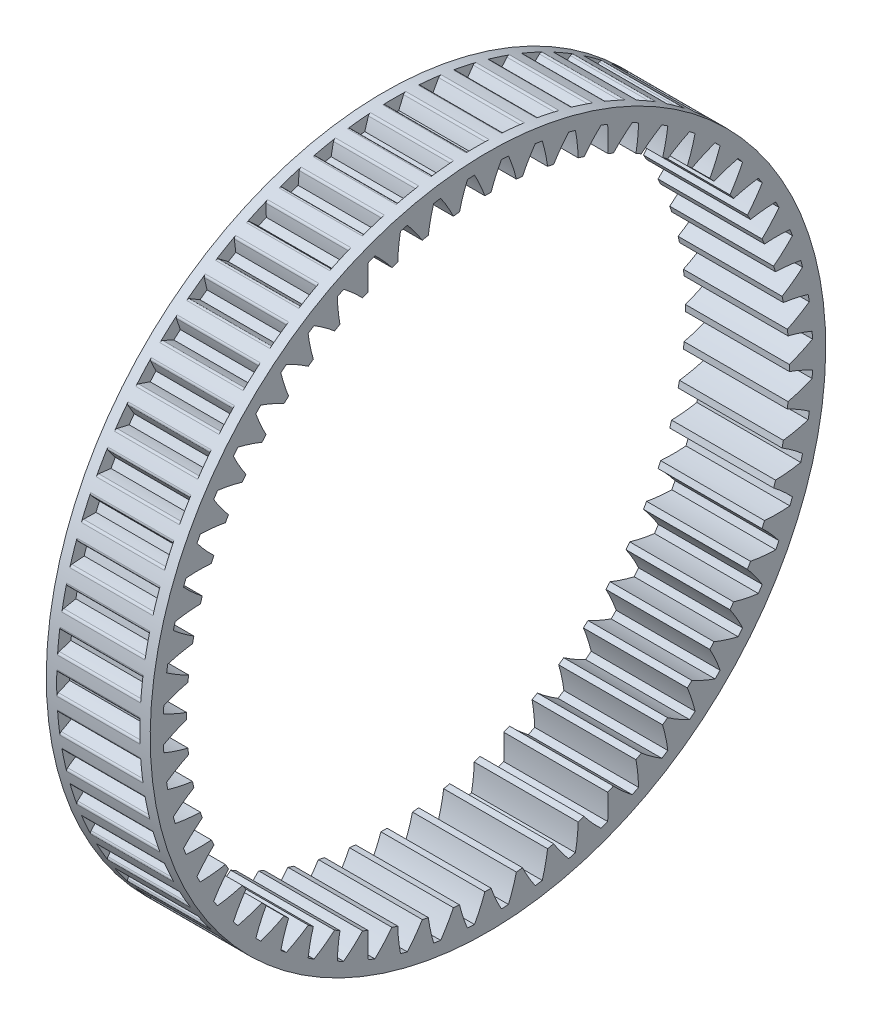
SolidWorks part; units mm, degrees
material "AISI 1020"
ref_plane "Front Plane" through (0, 0, 0) normal (0, 0, 1) x (1, 0, 0)
ref_plane "Top Plane" through (0, 0, 0) normal (0, 1, 0) x (1, 0, 0)
ref_plane "Right Plane" through (0, 0, 0) normal (1, 0, 0) x (0, 0, -1)
ref_plane "Plane1" through (10, 0, 0) normal (1, 0, 0) x (0, 0, -1)
sketch "Sketch1" plane through (10, 0, 0) normal (1, 0, 0) x (0, 0, -1)
  circle A0 centre (0, 0) radius 32.5
  arc A1 (1.8156, 28.9431) -> (2.9287, 31.1135) centre (15.6748, 23.2053) cw
  arc A2 (2.9287, 31.1135) -> (3.6041, 31.0425) centre (0, 0) cw
  arc A3 (3.6041, 31.0425) -> (4.2417, 28.6881) centre (-10.5076, 25.9572) cw
  arc A4 (4.2417, 28.6881) -> (4.831, 28.5948) centre (0, 0) cw
  arc A5 (4.831, 28.5948) -> (6.1649, 30.6369) centre (18.0145, 21.4397) cw
  arc A6 (6.1649, 30.6369) -> (6.8292, 30.4957) centre (0, 0) cw
  arc A7 (6.8292, 30.4957) -> (7.2172, 28.0876) centre (-7.7368, 26.9133) cw
  arc A8 (7.2172, 28.0876) -> (7.7935, 27.9332) centre (0, 0) cw
  arc A9 (7.7935, 27.9332) -> (9.3336, 29.8246) centre (20.1569, 19.4393) cw
  arc A10 (9.3336, 29.8246) -> (9.9794, 29.6148) centre (0, 0) cw
  arc A11 (9.9794, 29.6148) -> (10.1136, 27.1793) centre (-4.8812, 27.5746) cw
  arc A12 (10.1136, 27.1793) -> (10.6706, 26.9655) centre (0, 0) cw
  arc A13 (10.6706, 26.9655) -> (12.4, 28.6856) centre (22.0784, 17.2258) cw
  arc A14 (12.4, 28.6856) -> (13.0204, 28.4094) centre (0, 0) cw
  arc A15 (13.0204, 28.4094) -> (12.8992, 25.9733) centre (-1.9721, 27.9338) cw
  arc A16 (12.8992, 25.9733) -> (13.4308, 25.7024) centre (0, 0) cw
  arc A17 (13.4308, 25.7024) -> (15.3305, 27.2323) centre (23.7581, 14.8236) cw
  arc A18 (15.3305, 27.2323) -> (15.9186, 26.8928) centre (0, 0) cw
  arc A19 (15.9186, 26.8928) -> (15.5435, 24.4826) centre (0.9586, 27.9869) cw
  arc A20 (15.5435, 24.4826) -> (16.0439, 24.1577) centre (0, 0) cw
  arc A21 (16.0439, 24.1577) -> (18.0931, 25.4807) centre (25.1774, 12.259) cw
  arc A22 (18.0931, 25.4807) -> (18.6425, 25.0815) centre (0, 0) cw
  arc A23 (18.6425, 25.0815) -> (18.0175, 22.7238) centre (3.8788, 27.7334) cw
  arc A24 (18.0175, 22.7238) -> (18.4812, 22.3483) centre (0, 0) cw
  arc A25 (18.4812, 22.3483) -> (20.6574, 23.4498) centre (26.3209, 9.5601) cw
  arc A26 (20.6574, 23.4498) -> (21.1621, 22.9954) centre (0, 0) cw
  arc A27 (21.1621, 22.9954) -> (20.2941, 20.7159) centre (6.7564, 27.176) cw
  arc A28 (20.2941, 20.7159) -> (20.7159, 20.2941) centre (0, 0) cw
  arc A29 (20.7159, 20.2941) -> (22.9954, 21.1621) centre (27.176, 6.7564) cw
  arc A30 (22.9954, 21.1621) -> (23.4498, 20.6574) centre (0, 0) cw
  arc A31 (23.4498, 20.6574) -> (22.3483, 18.4812) centre (9.5601, 26.3209) cw
  arc A32 (22.3483, 18.4812) -> (22.7238, 18.0175) centre (0, 0) cw
  arc A33 (22.7238, 18.0175) -> (25.0815, 18.6425) centre (27.7334, 3.8788) cw
  arc A34 (25.0815, 18.6425) -> (25.4807, 18.0931) centre (0, 0) cw
  arc A35 (25.4807, 18.0931) -> (24.1577, 16.0439) centre (12.259, 25.1774) cw
  arc A36 (24.1577, 16.0439) -> (24.4826, 15.5435) centre (0, 0) cw
  arc A37 (24.4826, 15.5435) -> (26.8928, 15.9186) centre (27.9869, 0.9586) cw
  arc A38 (26.8928, 15.9186) -> (27.2323, 15.3305) centre (0, 0) cw
  arc A39 (27.2323, 15.3305) -> (25.7024, 13.4308) centre (14.8236, 23.7581) cw
  arc A40 (25.7024, 13.4308) -> (25.9733, 12.8992) centre (0, 0) cw
  arc A41 (25.9733, 12.8992) -> (28.4094, 13.0204) centre (27.9338, -1.9721) cw
  arc A42 (28.4094, 13.0204) -> (28.6856, 12.4) centre (0, 0) cw
  arc A43 (28.6856, 12.4) -> (26.9655, 10.6706) centre (17.2258, 22.0784) cw
  arc A44 (26.9655, 10.6706) -> (27.1793, 10.1136) centre (0, 0) cw
  arc A45 (27.1793, 10.1136) -> (29.6148, 9.9794) centre (27.5746, -4.8812) cw
  arc A46 (29.6148, 9.9794) -> (29.8246, 9.3336) centre (0, 0) cw
  arc A47 (29.8246, 9.3336) -> (27.9332, 7.7935) centre (19.4393, 20.1569) cw
  arc A48 (27.9332, 7.7935) -> (28.0876, 7.2172) centre (0, 0) cw
  arc A49 (28.0876, 7.2172) -> (30.4957, 6.8292) centre (26.9133, -7.7368) cw
  arc A50 (30.4957, 6.8292) -> (30.6369, 6.1649) centre (0, 0) cw
  arc A51 (30.6369, 6.1649) -> (28.5948, 4.831) centre (21.4397, 18.0145) cw
  arc A52 (28.5948, 4.831) -> (28.6881, 4.2417) centre (0, 0) cw
  arc A53 (28.6881, 4.2417) -> (31.0425, 3.6041) centre (25.9572, -10.5076) cw
  arc A54 (31.0425, 3.6041) -> (31.1135, 2.9287) centre (0, 0) cw
  arc A55 (31.1135, 2.9287) -> (28.9431, 1.8156) centre (23.2053, 15.6748) cw
  arc A56 (28.9431, 1.8156) -> (28.9743, 1.2198) centre (0, 0) cw
  arc A57 (28.9743, 1.2198) -> (31.2492, 0.3395) centre (24.7167, -13.1633) cw
  arc A58 (31.2492, 0.3395) -> (31.2492, -0.3395) centre (0, 0) cw
  arc A59 (31.2492, -0.3395) -> (28.9743, -1.2198) centre (24.7167, 13.1633) cw
  arc A60 (28.9743, -1.2198) -> (28.9431, -1.8156) centre (0, 0) cw
  arc A61 (28.9431, -1.8156) -> (31.1135, -2.9287) centre (23.2053, -15.6748) cw
  arc A62 (31.1135, -2.9287) -> (31.0425, -3.6041) centre (0, 0) cw
  arc A63 (31.0425, -3.6041) -> (28.6881, -4.2417) centre (25.9572, 10.5076) cw
  arc A64 (28.6881, -4.2417) -> (28.5948, -4.831) centre (0, 0) cw
  arc A65 (28.5948, -4.831) -> (30.6369, -6.1649) centre (21.4397, -18.0145) cw
  arc A66 (30.6369, -6.1649) -> (30.4957, -6.8292) centre (0, 0) cw
  arc A67 (30.4957, -6.8292) -> (28.0876, -7.2172) centre (26.9133, 7.7368) cw
  arc A68 (28.0876, -7.2172) -> (27.9332, -7.7935) centre (0, 0) cw
  arc A69 (27.9332, -7.7935) -> (29.8246, -9.3336) centre (19.4393, -20.1569) cw
  arc A70 (29.8246, -9.3336) -> (29.6148, -9.9794) centre (0, 0) cw
  arc A71 (29.6148, -9.9794) -> (27.1793, -10.1136) centre (27.5746, 4.8812) cw
  arc A72 (27.1793, -10.1136) -> (26.9655, -10.6706) centre (0, 0) cw
  arc A73 (26.9655, -10.6706) -> (28.6856, -12.4) centre (17.2258, -22.0784) cw
  arc A74 (28.6856, -12.4) -> (28.4094, -13.0204) centre (0, 0) cw
  arc A75 (28.4094, -13.0204) -> (25.9733, -12.8992) centre (27.9338, 1.9721) cw
  arc A76 (25.9733, -12.8992) -> (25.7024, -13.4308) centre (0, 0) cw
  arc A77 (25.7024, -13.4308) -> (27.2323, -15.3305) centre (14.8236, -23.7581) cw
  arc A78 (27.2323, -15.3305) -> (26.8928, -15.9186) centre (0, 0) cw
  arc A79 (26.8928, -15.9186) -> (24.4826, -15.5435) centre (27.9869, -0.9586) cw
  arc A80 (24.4826, -15.5435) -> (24.1577, -16.0439) centre (0, 0) cw
  arc A81 (24.1577, -16.0439) -> (25.4807, -18.0931) centre (12.259, -25.1774) cw
  arc A82 (25.4807, -18.0931) -> (25.0815, -18.6425) centre (0, 0) cw
  arc A83 (25.0815, -18.6425) -> (22.7238, -18.0175) centre (27.7334, -3.8788) cw
  arc A84 (22.7238, -18.0175) -> (22.3483, -18.4812) centre (0, 0) cw
  arc A85 (22.3483, -18.4812) -> (23.4498, -20.6574) centre (9.5601, -26.3209) cw
  arc A86 (23.4498, -20.6574) -> (22.9954, -21.1621) centre (0, 0) cw
  arc A87 (22.9954, -21.1621) -> (20.7159, -20.2941) centre (27.176, -6.7564) cw
  arc A88 (20.7159, -20.2941) -> (20.2941, -20.7159) centre (0, 0) cw
  arc A89 (20.2941, -20.7159) -> (21.1621, -22.9954) centre (6.7564, -27.176) cw
  arc A90 (21.1621, -22.9954) -> (20.6574, -23.4498) centre (0, 0) cw
  arc A91 (20.6574, -23.4498) -> (18.4812, -22.3483) centre (26.3209, -9.5601) cw
  arc A92 (18.4812, -22.3483) -> (18.0175, -22.7238) centre (0, 0) cw
  arc A93 (18.0175, -22.7238) -> (18.6425, -25.0815) centre (3.8788, -27.7334) cw
  arc A94 (18.6425, -25.0815) -> (18.0931, -25.4807) centre (0, 0) cw
  arc A95 (18.0931, -25.4807) -> (16.0439, -24.1577) centre (25.1774, -12.259) cw
  arc A96 (16.0439, -24.1577) -> (15.5435, -24.4826) centre (0, 0) cw
  arc A97 (15.5435, -24.4826) -> (15.9186, -26.8928) centre (0.9586, -27.9869) cw
  arc A98 (15.9186, -26.8928) -> (15.3305, -27.2323) centre (0, 0) cw
  arc A99 (15.3305, -27.2323) -> (13.4308, -25.7024) centre (23.7581, -14.8236) cw
  arc A100 (13.4308, -25.7024) -> (12.8992, -25.9733) centre (0, 0) cw
  arc A101 (12.8992, -25.9733) -> (13.0204, -28.4094) centre (-1.9721, -27.9338) cw
  arc A102 (13.0204, -28.4094) -> (12.4, -28.6856) centre (0, 0) cw
  arc A103 (12.4, -28.6856) -> (10.6706, -26.9655) centre (22.0784, -17.2258) cw
  arc A104 (10.6706, -26.9655) -> (10.1136, -27.1793) centre (0, 0) cw
  arc A105 (10.1136, -27.1793) -> (9.9794, -29.6148) centre (-4.8812, -27.5746) cw
  arc A106 (9.9794, -29.6148) -> (9.3336, -29.8246) centre (0, 0) cw
  arc A107 (9.3336, -29.8246) -> (7.7935, -27.9332) centre (20.1569, -19.4393) cw
  arc A108 (7.7935, -27.9332) -> (7.2172, -28.0876) centre (0, 0) cw
  arc A109 (7.2172, -28.0876) -> (6.8292, -30.4957) centre (-7.7368, -26.9133) cw
  arc A110 (6.8292, -30.4957) -> (6.1649, -30.6369) centre (0, 0) cw
  arc A111 (6.1649, -30.6369) -> (4.831, -28.5948) centre (18.0145, -21.4397) cw
  arc A112 (4.831, -28.5948) -> (4.2417, -28.6881) centre (0, 0) cw
  arc A113 (4.2417, -28.6881) -> (3.6041, -31.0425) centre (-10.5076, -25.9572) cw
  arc A114 (3.6041, -31.0425) -> (2.9287, -31.1135) centre (0, 0) cw
  arc A115 (2.9287, -31.1135) -> (1.8156, -28.9431) centre (15.6748, -23.2053) cw
  arc A116 (1.8156, -28.9431) -> (1.2198, -28.9743) centre (0, 0) cw
  arc A117 (1.2198, -28.9743) -> (0.3395, -31.2492) centre (-13.1633, -24.7167) cw
  arc A118 (0.3395, -31.2492) -> (-0.3395, -31.2492) centre (0, 0) cw
  arc A119 (-0.3395, -31.2492) -> (-1.2198, -28.9743) centre (13.1633, -24.7167) cw
  arc A120 (-1.2198, -28.9743) -> (-1.8156, -28.9431) centre (0, 0) cw
  arc A121 (-1.8156, -28.9431) -> (-2.9287, -31.1135) centre (-15.6748, -23.2053) cw
  arc A122 (-2.9287, -31.1135) -> (-3.6041, -31.0425) centre (0, 0) cw
  arc A123 (-3.6041, -31.0425) -> (-4.2417, -28.6881) centre (10.5076, -25.9572) cw
  arc A124 (-4.2417, -28.6881) -> (-4.831, -28.5948) centre (0, 0) cw
  arc A125 (-4.831, -28.5948) -> (-6.1649, -30.6369) centre (-18.0145, -21.4397) cw
  arc A126 (-6.1649, -30.6369) -> (-6.8292, -30.4957) centre (0, 0) cw
  arc A127 (-6.8292, -30.4957) -> (-7.2172, -28.0876) centre (7.7368, -26.9133) cw
  arc A128 (-7.2172, -28.0876) -> (-7.7935, -27.9332) centre (0, 0) cw
  arc A129 (-7.7935, -27.9332) -> (-9.3336, -29.8246) centre (-20.1569, -19.4393) cw
  arc A130 (-9.3336, -29.8246) -> (-9.9794, -29.6148) centre (0, 0) cw
  arc A131 (-9.9794, -29.6148) -> (-10.1136, -27.1793) centre (4.8812, -27.5746) cw
  arc A132 (-10.1136, -27.1793) -> (-10.6706, -26.9655) centre (0, 0) cw
  arc A133 (-10.6706, -26.9655) -> (-12.4, -28.6856) centre (-22.0784, -17.2258) cw
  arc A134 (-12.4, -28.6856) -> (-13.0204, -28.4094) centre (0, 0) cw
  arc A135 (-13.0204, -28.4094) -> (-12.8992, -25.9733) centre (1.9721, -27.9338) cw
  arc A136 (-12.8992, -25.9733) -> (-13.4308, -25.7024) centre (0, 0) cw
  arc A137 (-13.4308, -25.7024) -> (-15.3305, -27.2323) centre (-23.7581, -14.8236) cw
  arc A138 (-15.3305, -27.2323) -> (-15.9186, -26.8928) centre (0, 0) cw
  arc A139 (-15.9186, -26.8928) -> (-15.5435, -24.4826) centre (-0.9586, -27.9869) cw
  arc A140 (-15.5435, -24.4826) -> (-16.0439, -24.1577) centre (0, 0) cw
  arc A141 (-16.0439, -24.1577) -> (-18.0931, -25.4807) centre (-25.1774, -12.259) cw
  arc A142 (-18.0931, -25.4807) -> (-18.6425, -25.0815) centre (0, 0) cw
  arc A143 (-18.6425, -25.0815) -> (-18.0175, -22.7238) centre (-3.8788, -27.7334) cw
  arc A144 (-18.0175, -22.7238) -> (-18.4812, -22.3483) centre (0, 0) cw
  arc A145 (-18.4812, -22.3483) -> (-20.6574, -23.4498) centre (-26.3209, -9.5601) cw
  arc A146 (-20.6574, -23.4498) -> (-21.1621, -22.9954) centre (0, 0) cw
  arc A147 (-21.1621, -22.9954) -> (-20.2941, -20.7159) centre (-6.7564, -27.176) cw
  arc A148 (-20.2941, -20.7159) -> (-20.7159, -20.2941) centre (0, 0) cw
  arc A149 (-20.7159, -20.2941) -> (-22.9954, -21.1621) centre (-27.176, -6.7564) cw
  arc A150 (-22.9954, -21.1621) -> (-23.4498, -20.6574) centre (0, 0) cw
  arc A151 (-23.4498, -20.6574) -> (-22.3483, -18.4812) centre (-9.5601, -26.3209) cw
  arc A152 (-22.3483, -18.4812) -> (-22.7238, -18.0175) centre (0, 0) cw
  arc A153 (-22.7238, -18.0175) -> (-25.0815, -18.6425) centre (-27.7334, -3.8788) cw
  arc A154 (-25.0815, -18.6425) -> (-25.4807, -18.0931) centre (0, 0) cw
  arc A155 (-25.4807, -18.0931) -> (-24.1577, -16.0439) centre (-12.259, -25.1774) cw
  arc A156 (-24.1577, -16.0439) -> (-24.4826, -15.5435) centre (0, 0) cw
  arc A157 (-24.4826, -15.5435) -> (-26.8928, -15.9186) centre (-27.9869, -0.9586) cw
  arc A158 (-26.8928, -15.9186) -> (-27.2323, -15.3305) centre (0, 0) cw
  arc A159 (-27.2323, -15.3305) -> (-25.7024, -13.4308) centre (-14.8236, -23.7581) cw
  arc A160 (-25.7024, -13.4308) -> (-25.9733, -12.8992) centre (0, 0) cw
  arc A161 (-25.9733, -12.8992) -> (-28.4094, -13.0204) centre (-27.9338, 1.9721) cw
  arc A162 (-28.4094, -13.0204) -> (-28.6856, -12.4) centre (0, 0) cw
  arc A163 (-28.6856, -12.4) -> (-26.9655, -10.6706) centre (-17.2258, -22.0784) cw
  arc A164 (-26.9655, -10.6706) -> (-27.1793, -10.1136) centre (0, 0) cw
  arc A165 (-27.1793, -10.1136) -> (-29.6148, -9.9794) centre (-27.5746, 4.8812) cw
  arc A166 (-29.6148, -9.9794) -> (-29.8246, -9.3336) centre (0, 0) cw
  arc A167 (-29.8246, -9.3336) -> (-27.9332, -7.7935) centre (-19.4393, -20.1569) cw
  arc A168 (-27.9332, -7.7935) -> (-28.0876, -7.2172) centre (0, 0) cw
  arc A169 (-28.0876, -7.2172) -> (-30.4957, -6.8292) centre (-26.9133, 7.7368) cw
  arc A170 (-30.4957, -6.8292) -> (-30.6369, -6.1649) centre (0, 0) cw
  arc A171 (-30.6369, -6.1649) -> (-28.5948, -4.831) centre (-21.4397, -18.0145) cw
  arc A172 (-28.5948, -4.831) -> (-28.6881, -4.2417) centre (0, 0) cw
  arc A173 (-28.6881, -4.2417) -> (-31.0425, -3.6041) centre (-25.9572, 10.5076) cw
  arc A174 (-31.0425, -3.6041) -> (-31.1135, -2.9287) centre (0, 0) cw
  arc A175 (-31.1135, -2.9287) -> (-28.9431, -1.8156) centre (-23.2053, -15.6748) cw
  arc A176 (-28.9431, -1.8156) -> (-28.9743, -1.2198) centre (0, 0) cw
  arc A177 (-28.9743, -1.2198) -> (-31.2492, -0.3395) centre (-24.7167, 13.1633) cw
  arc A178 (-31.2492, -0.3395) -> (-31.2492, 0.3395) centre (0, 0) cw
  arc A179 (-31.2492, 0.3395) -> (-28.9743, 1.2198) centre (-24.7167, -13.1633) cw
  arc A180 (-28.9743, 1.2198) -> (-28.9431, 1.8156) centre (0, 0) cw
  arc A181 (-28.9431, 1.8156) -> (-31.1135, 2.9287) centre (-23.2053, 15.6748) cw
  arc A182 (-31.1135, 2.9287) -> (-31.0425, 3.6041) centre (0, 0) cw
  arc A183 (-31.0425, 3.6041) -> (-28.6881, 4.2417) centre (-25.9572, -10.5076) cw
  arc A184 (-28.6881, 4.2417) -> (-28.5948, 4.831) centre (0, 0) cw
  arc A185 (-28.5948, 4.831) -> (-30.6369, 6.1649) centre (-21.4397, 18.0145) cw
  arc A186 (-30.6369, 6.1649) -> (-30.4957, 6.8292) centre (0, 0) cw
  arc A187 (-30.4957, 6.8292) -> (-28.0876, 7.2172) centre (-26.9133, -7.7368) cw
  arc A188 (-28.0876, 7.2172) -> (-27.9332, 7.7935) centre (0, 0) cw
  arc A189 (-27.9332, 7.7935) -> (-29.8246, 9.3336) centre (-19.4393, 20.1569) cw
  arc A190 (-29.8246, 9.3336) -> (-29.6148, 9.9794) centre (0, 0) cw
  arc A191 (-29.6148, 9.9794) -> (-27.1793, 10.1136) centre (-27.5746, -4.8812) cw
  arc A192 (-27.1793, 10.1136) -> (-26.9655, 10.6706) centre (0, 0) cw
  arc A193 (-26.9655, 10.6706) -> (-28.6856, 12.4) centre (-17.2258, 22.0784) cw
  arc A194 (-28.6856, 12.4) -> (-28.4094, 13.0204) centre (0, 0) cw
  arc A195 (-28.4094, 13.0204) -> (-25.9733, 12.8992) centre (-27.9338, -1.9721) cw
  arc A196 (-25.9733, 12.8992) -> (-25.7024, 13.4308) centre (0, 0) cw
  arc A197 (-25.7024, 13.4308) -> (-27.2323, 15.3305) centre (-14.8236, 23.7581) cw
  arc A198 (-27.2323, 15.3305) -> (-26.8928, 15.9186) centre (0, 0) cw
  arc A199 (-26.8928, 15.9186) -> (-24.4826, 15.5435) centre (-27.9869, 0.9586) cw
  arc A200 (-24.4826, 15.5435) -> (-24.1577, 16.0439) centre (0, 0) cw
  arc A201 (-24.1577, 16.0439) -> (-25.4807, 18.0931) centre (-12.259, 25.1774) cw
  arc A202 (-25.4807, 18.0931) -> (-25.0815, 18.6425) centre (0, 0) cw
  arc A203 (-25.0815, 18.6425) -> (-22.7238, 18.0175) centre (-27.7334, 3.8788) cw
  arc A204 (-22.7238, 18.0175) -> (-22.3483, 18.4812) centre (0, 0) cw
  arc A205 (-22.3483, 18.4812) -> (-23.4498, 20.6574) centre (-9.5601, 26.3209) cw
  arc A206 (-23.4498, 20.6574) -> (-22.9954, 21.1621) centre (0, 0) cw
  arc A207 (-22.9954, 21.1621) -> (-20.7159, 20.2941) centre (-27.176, 6.7564) cw
  arc A208 (-20.7159, 20.2941) -> (-20.2941, 20.7159) centre (0, 0) cw
  arc A209 (-20.2941, 20.7159) -> (-21.1621, 22.9954) centre (-6.7564, 27.176) cw
  arc A210 (-21.1621, 22.9954) -> (-20.6574, 23.4498) centre (0, 0) cw
  arc A211 (-20.6574, 23.4498) -> (-18.4812, 22.3483) centre (-26.3209, 9.5601) cw
  arc A212 (-18.4812, 22.3483) -> (-18.0175, 22.7238) centre (0, 0) cw
  arc A213 (-18.0175, 22.7238) -> (-18.6425, 25.0815) centre (-3.8788, 27.7334) cw
  arc A214 (-18.6425, 25.0815) -> (-18.0931, 25.4807) centre (0, 0) cw
  arc A215 (-18.0931, 25.4807) -> (-16.0439, 24.1577) centre (-25.1774, 12.259) cw
  arc A216 (-16.0439, 24.1577) -> (-15.5435, 24.4826) centre (0, 0) cw
  arc A217 (-15.5435, 24.4826) -> (-15.9186, 26.8928) centre (-0.9586, 27.9869) cw
  arc A218 (-15.9186, 26.8928) -> (-15.3305, 27.2323) centre (0, 0) cw
  arc A219 (-15.3305, 27.2323) -> (-13.4308, 25.7024) centre (-23.7581, 14.8236) cw
  arc A220 (-13.4308, 25.7024) -> (-12.8992, 25.9733) centre (0, 0) cw
  arc A221 (-12.8992, 25.9733) -> (-13.0204, 28.4094) centre (1.9721, 27.9338) cw
  arc A222 (-13.0204, 28.4094) -> (-12.4, 28.6856) centre (0, 0) cw
  arc A223 (-12.4, 28.6856) -> (-10.6706, 26.9655) centre (-22.0784, 17.2258) cw
  arc A224 (-10.6706, 26.9655) -> (-10.1136, 27.1793) centre (0, 0) cw
  arc A225 (-10.1136, 27.1793) -> (-9.9794, 29.6148) centre (4.8812, 27.5746) cw
  arc A226 (-9.9794, 29.6148) -> (-9.3336, 29.8246) centre (0, 0) cw
  arc A227 (-9.3336, 29.8246) -> (-7.7935, 27.9332) centre (-20.1569, 19.4393) cw
  arc A228 (-7.7935, 27.9332) -> (-7.2172, 28.0876) centre (0, 0) cw
  arc A229 (-7.2172, 28.0876) -> (-6.8292, 30.4957) centre (7.7368, 26.9133) cw
  arc A230 (-6.8292, 30.4957) -> (-6.1649, 30.6369) centre (0, 0) cw
  arc A231 (-6.1649, 30.6369) -> (-4.831, 28.5948) centre (-18.0145, 21.4397) cw
  arc A232 (-4.831, 28.5948) -> (-4.2417, 28.6881) centre (0, 0) cw
  arc A233 (-4.2417, 28.6881) -> (-3.6041, 31.0425) centre (10.5076, 25.9572) cw
  arc A234 (-3.6041, 31.0425) -> (-2.9287, 31.1135) centre (0, 0) cw
  arc A235 (-2.9287, 31.1135) -> (-1.8156, 28.9431) centre (-15.6748, 23.2053) cw
  arc A236 (-1.8156, 28.9431) -> (-1.2198, 28.9743) centre (0, 0) cw
  arc A237 (-1.2198, 28.9743) -> (-0.3395, 31.2492) centre (13.1633, 24.7167) cw
  arc A238 (-0.3395, 31.2492) -> (0.3395, 31.2492) centre (0, 0) cw
  arc A239 (0.3395, 31.2492) -> (1.2198, 28.9743) centre (-13.1633, 24.7167) cw
  arc A240 (1.2198, 28.9743) -> (1.8156, 28.9431) centre (0, 0) cw
extrude "Boss-Extrude1" add sketch "Sketch1" against normal blind 10
sketch "Sketch2" plane through (10, 0, 0) normal (1, 0, 0) x (0, 0, -1)
  line L0 (0, 0) -> (32.5, 0) construction
  line L1 (0, 0) -> (28.9603, 1.5177) construction
  circle A0 centre (0, 0) radius 32.5 construction
  arc A1 (28.9743, 1.2198) -> (28.9431, 1.8156) centre (0, 0) ccw construction
move or copy body "Body-Move/Copy1" bodies to move or copy 103 copy no rotation origin (0, 0, 0) rotation axis (1, 0, 0) rotation angle 3
sketch "Sketch3" plane through (10, 0, 0) normal (1, 0, 0) x (0, 0, -1)
  line L0 (0, 0) -> (32.5, 0) construction
  line L1 (0, 0) -> (32.5, 0) construction
  arc A0 (31.2519, -0.4165) -> (31.2519, 0.4165) centre (0, 0) ccw
  arc A1 (32.9602, -1.1987) -> (32.9602, 1.1987) centre (0, 0) ccw
  spline S0 degree 4 poles (31.1089, 0.3655) (31.117, 0.3683) (31.1401, 0.3764) (31.1637, 0.3846) (31.2347, 0.4102) (31.2655, 0.4214) (31.3459, 0.4511) (31.3929, 0.4691) (31.4573, 0.4937) (31.511, 0.5149) (31.5709, 0.5387) (31.6269, 0.5613) (31.6851, 0.5852) (31.7417, 0.6088) (31.7991, 0.6331) (31.8557, 0.6574) (31.9128, 0.6823) (31.9742, 0.7094) (32.0507, 0.7437) (32.1389, 0.7839) (32.2445, 0.8335) (32.3528, 0.8851) (32.4693, 0.9426) (32.5715, 0.9935) (32.6957, 1.0577) (32.7823, 1.1026) (32.9208, 1.1772) (32.9729, 1.2055) (33.0468, 1.2463) (33.0913, 1.2711) (33.108, 1.2805) (33.1192, 1.2869) (33.1252, 1.2902) knots 0 0 0 0 0 0.017191 0.034381 0.068261 0.096159 0.124057 0.151954 0.179852 0.20775 0.235647 0.263545 0.291443 0.319341 0.347238 0.375136 0.403034 0.430932 0.468933 0.524728 0.580524 0.636319 0.692115 0.74791 0.803705 0.859501 0.915296 0.957648 0.978824 0.989412 1 1 1 1 1 construction
  spline S1 degree 4 poles (31.2519, 0.4165) (31.2642, 0.421) (31.2886, 0.4299) (31.3459, 0.4511) (31.3929, 0.4691) (31.4573, 0.4937) (31.511, 0.5149) (31.5709, 0.5387) (31.6269, 0.5613) (31.6851, 0.5852) (31.7417, 0.6088) (31.7991, 0.6331) (31.8557, 0.6574) (31.9128, 0.6823) (31.9742, 0.7094) (32.0507, 0.7437) (32.1389, 0.7839) (32.2445, 0.8335) (32.3528, 0.8851) (32.4693, 0.9426) (32.5715, 0.9935) (32.6957, 1.0577) (32.7823, 1.1026) (32.8929, 1.1621) (32.9372, 1.1861) (32.9602, 1.1987) knots 0.068261 0.068261 0.068261 0.068261 0.068261 0.096159 0.124057 0.151954 0.179852 0.20775 0.235647 0.263545 0.291443 0.319341 0.347238 0.375136 0.403034 0.430932 0.468933 0.524728 0.580524 0.636319 0.692115 0.74791 0.803705 0.859501 0.915296 0.915296 0.915296 0.915296 0.915296
  spline S2 degree 4 poles (31.2519, -0.4165) (31.2642, -0.421) (31.2886, -0.4299) (31.3459, -0.4511) (31.3929, -0.4691) (31.4573, -0.4937) (31.511, -0.5149) (31.5709, -0.5387) (31.6269, -0.5613) (31.6851, -0.5852) (31.7417, -0.6088) (31.7991, -0.6331) (31.8557, -0.6574) (31.9128, -0.6823) (31.9742, -0.7094) (32.0507, -0.7437) (32.1389, -0.7839) (32.2445, -0.8335) (32.3528, -0.8851) (32.4693, -0.9426) (32.5715, -0.9935) (32.6957, -1.0577) (32.7823, -1.1026) (32.8929, -1.1621) (32.9372, -1.1861) (32.9602, -1.1987) knots 0.068261 0.068261 0.068261 0.068261 0.068261 0.096159 0.124057 0.151954 0.179852 0.20775 0.235647 0.263545 0.291443 0.319341 0.347238 0.375136 0.403034 0.430932 0.468933 0.524728 0.580524 0.636319 0.692115 0.74791 0.803705 0.859501 0.915296 0.915296 0.915296 0.915296 0.915296
  point P0 (0, 0)
extrude "Cut-Extrude1" cut sketch "Sketch3" against normal blind 8 from offset 1 offset against normal yes
fillet "Fillet1" radius 0.25 2 edges at (5, -0.951, -32.4861) (5, 0.951, -32.4861)
pattern_circular "CirPattern1" count 60 over 360 about axis through (0, 0, 0) along (1, 0, 0) of "Fillet1", "Cut-Extrude1"
